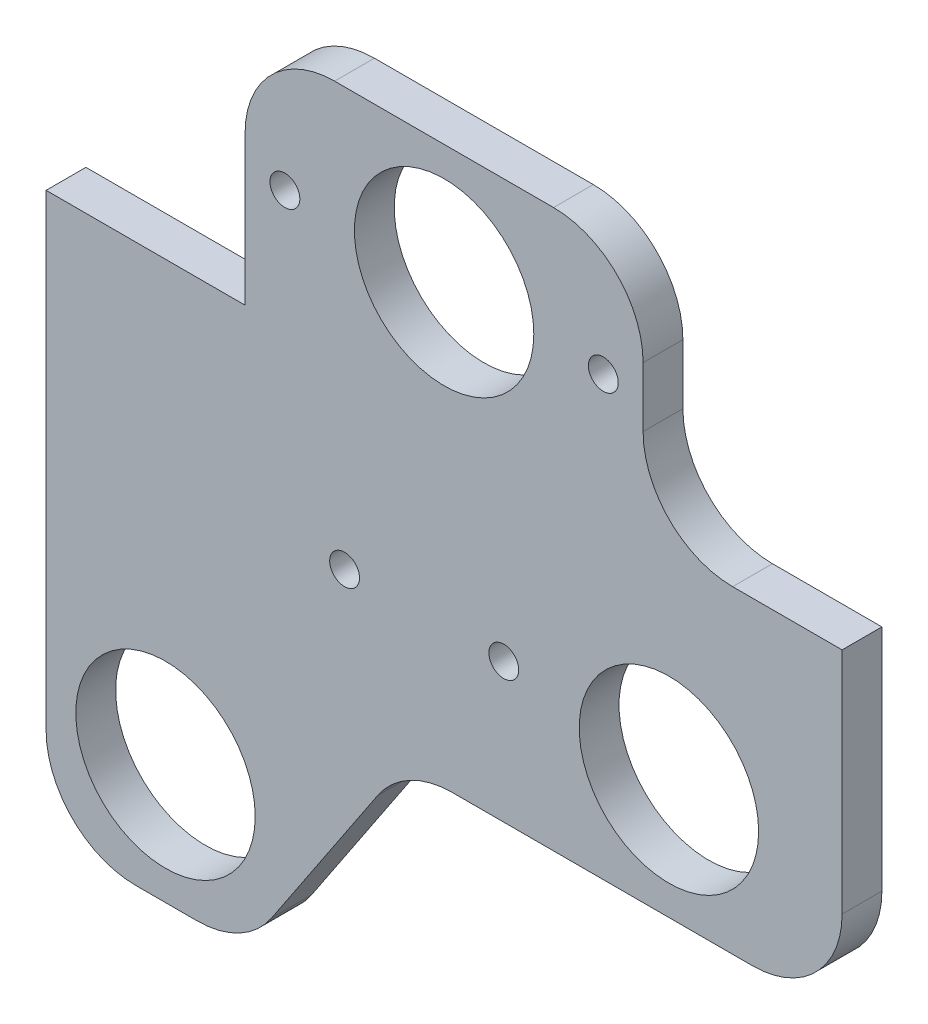
SolidWorks part; units mm, degrees
material "6063-T1"
ref_plane "Front Plane" through (0, 0, 0) normal (0, 0, 1) x (1, 0, 0)
ref_plane "Top Plane" through (0, 0, 0) normal (0, 1, 0) x (1, 0, 0)
ref_plane "Right Plane" through (0, 0, 0) normal (1, 0, 0) x (0, 0, -1)
sketch "Sketch1" plane through (0, 0, 0) normal (0, 0, 1) x (1, 0, 0)
  line L0 (63.5, -6.35) -> (-6.35, -6.35)
  line L1 (-63.5, 44.45) -> (63.5, 44.45)
  line L2 (-63.5, 44.45) -> (-63.5, -44.45)
  line L3 (-63.5, -44.45) -> (63.5, -44.45)
  line L4 (63.5, 44.45) -> (63.5, -44.45)
  line L5 (-63.5, 44.45) -> (63.5, -44.45) construction
  line L6 (-63.5, -44.45) -> (63.5, 44.45) construction
  line L7 (-6.35, -6.35) -> (-31.75, -44.45)
  circle A0 centre (-44.45, -25.4) radius 14.3129
  circle A1 centre (35.8719, 12.7) radius 14.3129
  point P0 (0, 0)
  dimension "D1" = 28.6258
  dimension "D2" = 28.6258
  dimension "D3" = 88.9
  dimension "D4" = 19.05
  dimension "D5" = 57.15
  dimension "D6" = 88.9
  dimension "D7" = 19.05
  dimension "D8" = 127
  dimension "D9" = 38.1
  dimension "D10" = 31.75
  dimension "D11" = 57.15
extrude "Boss-Extrude1" add sketch "Sketch1" along normal blind 6.35 contours L7 L0 L4 L1 L2 L3 A1 A0 region at (-9.2383, 13.2886, 0)
fillet "Fillet1" radius 14.2875 4 edges at (63.5, -6.35, 3.175) (-6.35, -6.35, 3.175) (-31.75, -44.45, 3.175) (-63.5, -44.45, 3.175)
sketch "Sketch2" plane through (0, 0, 6.35) normal (0, 0, 1) x (1, 0, 0)
  line L0 (-63.5, 44.45) -> (63.5, 44.45) construction
  line L1 (-31.75, 44.45) -> (31.75, 44.45)
  line L2 (-31.75, 44.45) -> (-31.75, 82.55)
  line L3 (-31.75, 82.55) -> (31.75, 82.55)
  line L4 (31.75, 44.45) -> (31.75, 82.55)
  line L5 (-63.5, 44.45) -> (-63.5, -30.1625) construction
  dimension "D1" = 38.1
  dimension "D2" = 31.75
  dimension "D3" = 63.5
extrude "Boss-Extrude2" add sketch "Sketch2" against normal blind 6.35
fillet "Fillet2" radius 14.2875 3 edges at (-31.75, 82.55, 3.175) (31.75, 82.55, 3.175) (31.75, 44.45, 3.175)
sketch "Sketch3" plane through (0, 0, 6.35) normal (0, 0, 1) x (1, 0, 0)
  line L1 (17.4625, 82.55) -> (-17.4625, 82.55) construction
  circle A0 centre (0, 63.5) radius 14.3129
  circle A1 centre (35.8719, 12.7) radius 14.3129 construction
  dimension "D1" = 28.6258
  dimension "D2" = 35.8719
  dimension "D3" = 19.05
extrude "Cut-Extrude1" cut sketch "Sketch3" against normal through all
sketch "Sketch4" plane through (0, 0, 6.35) normal (0, 0, 1) x (1, 0, 0)
  circle A0 centre (-25.4, 63.5) radius 2.3813
  circle A1 centre (25.4, 63.5) radius 2.3813
  circle A2 centre (0, 63.5) radius 14.2875
  circle A3 centre (0, 63.5) radius 25.4 construction
  dimension "D1" = 50.8
  dimension "D2" = 4.7625
  dimension "D3" = 4.7625
extrude "Cut-Extrude2" cut sketch "Sketch4" against normal through all
sketch "Sketch5" plane through (0, 0, 6.35) normal (0, 0, 1) x (1, 0, 0)
  circle A0 centre (-15.875, 15.875) radius 2.3813
  circle A1 centre (9.525, 15.875) radius 2.3813
  point P4 (-15.875, 15.875)
  dimension "D1" = 4.7625
  dimension "D2" = 4.7625
  dimension "D3" = 25.4
  dimension "D4" = 15.875
  dimension "D5" = 9.525
extrude "Cut-Extrude3" cut sketch "Sketch5" against normal through all
